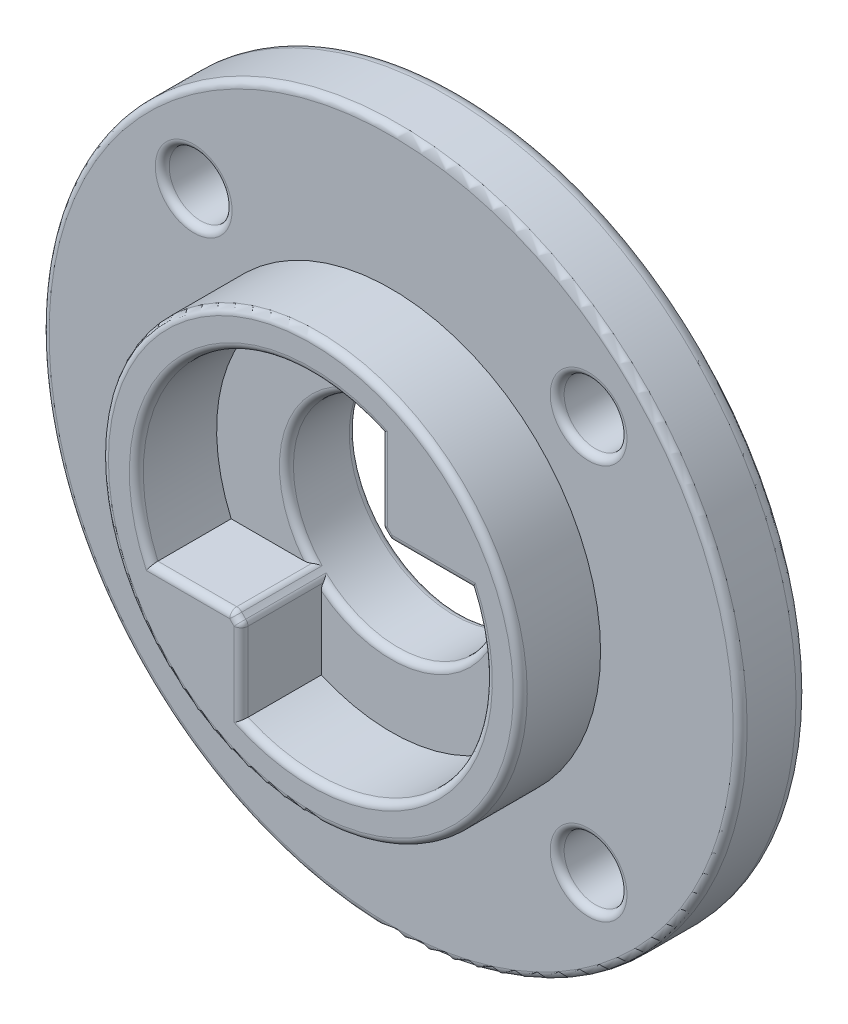
SolidWorks part; units mm, degrees
ref_plane "Front Plane" through (0, 0, 0) normal (0, 0, 1) x (1, 0, 0)
ref_plane "Top Plane" through (0, 0, 0) normal (0, 1, 0) x (1, 0, 0)
ref_plane "Right Plane" through (0, 0, 0) normal (1, 0, 0) x (0, 0, -1)
sketch "Sketch1" plane through (0, 0, 0) normal (0, 0, 1) x (1, 0, 0)
  line L0 (0, 0) -> (0, 25) construction
  line L1 (-17.6777, 17.6777) -> (-10.6066, 10.6066) construction
  line L2 (-10.6066, 10.6066) -> (0, 0) construction
  circle A0 centre (0, 0) radius 25
  circle A1 centre (0, 0) radius 15
  circle A2 centre (-14.1421, 14.1421) radius 2.25
  circle A3 centre (14.1421, 14.1421) radius 2.25
  circle A4 centre (14.1421, -14.1421) radius 2.25
  circle A5 centre (-14.1421, -14.1421) radius 2.25
  point P18 (0, 0)
  dimension "D1" = 50
  dimension "D2" = 10
  dimension "D3" = 45
  dimension "D4" = 4.5
  dimension "D5" = 4
extrude "Boss-Extrude1" add sketch "Sketch1" along normal blind 5
sketch "Sketch2" plane through (0, 0, 0) normal (0, 0, -1) x (-1, 0, 0)
  circle A0 centre (0, 0) radius 15
  circle A1 centre (0, 0) radius 15 construction
  circle A2 centre (0, 0) radius 12.5
  dimension "D1" = 25
extrude "Boss-Extrude2" add sketch "Sketch2" along normal blind 5.75 and the other way up to surface (5 mm away) other way up to face at (16.3921, -14.1421, 5)
sketch "Sketch3" plane through (0, 0, 0) normal (0, 0, 1) x (1, 0, 0)
  line L1 (-25, 5) -> (25, 5)
  line L2 (-25, 5) -> (-25, -5)
  line L3 (-25, -5) -> (25, -5)
  line L4 (25, 5) -> (25, -5)
  line L5 (-25, 5) -> (25, -5) construction
  line L6 (-25, -5) -> (25, 5) construction
  line L7 (5, -25) -> (-5, -25)
  line L8 (5, -25) -> (5, 25)
  line L9 (5, 25) -> (-5, 25)
  line L10 (-5, -25) -> (-5, 25)
  line L11 (5, -25) -> (-5, 25) construction
  line L12 (5, 25) -> (-5, -25) construction
  circle A0 centre (0, 0) radius 25 construction
  circle A1 centre (0, 0) radius 12.5
  circle A2 centre (0, 0) radius 12.5 construction
  point P0 (0, 0)
  point P6 (0, 0)
  dimension "D1" = 10
  dimension "D2" = 10
extrude "Boss-Extrude3" add sketch "Sketch3" against normal up to surface and the other way up to surface contours L1 A1 L8 | L3 A1 L10 region at (-7.4197, -7.4197, 0) region at (7.4197, 7.4197, 0) up to face at (-15, 0, -5.75) other way up to face at (16.3921, -14.1421, 5)
sketch "Sketch4" plane through (0, 0, 5) normal (0, 0, 1) x (1, 0, 0)
  circle A0 centre (0, 0) radius 12.5
  arc A1 (5, 11.4564) -> (-11.4564, -5) centre (0, 0) ccw construction
  circle A2 centre (0, 0) radius 7.5
  dimension "D1" = 15
extrude "Boss-Extrude4" add sketch "Sketch4" against normal blind 5
sketch "Sketch5" plane through (0, 0, 5) normal (0, 0, 1) x (1, 0, 0)
  circle A0 centre (0, 0) radius 7.5
  arc A1 (-5, -5.5902) -> (5.5902, 5) centre (0, 0) ccw construction
extrude "Cut-Extrude1" cut sketch "Sketch5" against normal through all
fillet "Fillet1" radius 0.5 25 edges at (8.5233, 5, -5.75) (8.8388, -8.8388, -5.75) (-5, -8.5233, -5.75) (-8.5233, -5, -5.75) (-8.8388, 8.8388, -5.75) (5, 8.5233, -5.75) (-15, 0, -5.75) (-5.5902, -5, -2.875) (-5.3033, -5.3033, -5.75) (-5, -5.5902, -2.875) (5.3033, -5.3033, 0) (5.5902, 5, -2.875) (5.3033, 5.3033, -5.75) (5, 5.5902, -2.875) (-5.3033, 5.3033, 0) (7.5, 0, 5) (16.3921, -14.1421, 0) (16.3921, -14.1421, 5) (16.3921, 14.1421, 0) (16.3921, 14.1421, 5) (-11.8921, 14.1421, 0) (-11.8921, 14.1421, 5) (-11.8921, -14.1421, 0) (-11.8921, -14.1421, 5) (25, 0, 0)
fillet "Fillet2" radius 1 1 edges at (25, 0, 5)
mirror "Mirror1" about plane through (0, 0, 0) normal (0, 0, 1) of bodies 105
delete or keep bodies "Body-Delete/Keep 1" type delete bodies bodies 105
